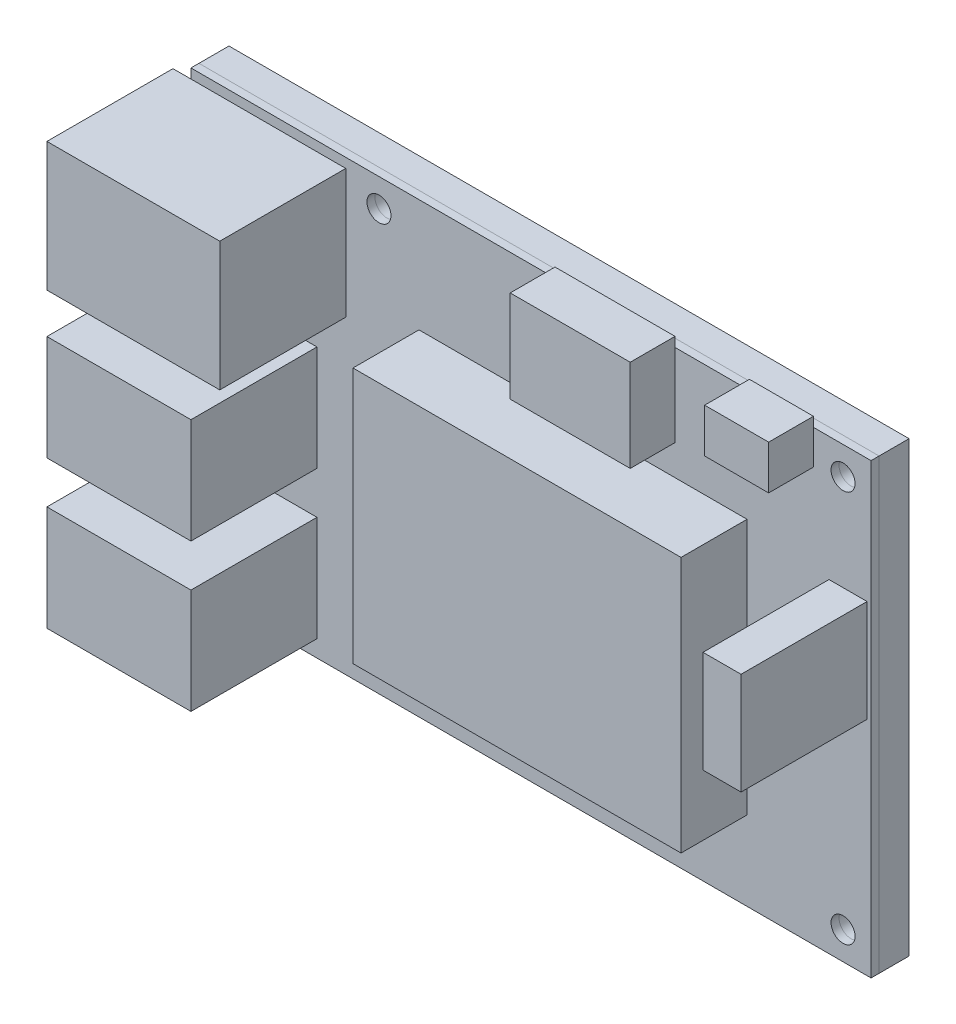
SolidWorks part; units mm, degrees
ref_plane "Front Plane" through (0, 0, 0) normal (0, 0, 1) x (1, 0, 0)
ref_plane "Top Plane" through (0, 0, 0) normal (0, 1, 0) x (1, 0, 0)
ref_plane "Right Plane" through (0, 0, 0) normal (1, 0, 0) x (0, 0, -1)
sketch "Sketch1" plane through (0, 0, 0) normal (0, 0, 1) x (1, 0, 0)
  line L0 (-19, 24.5) -> (39, 24.5) construction
  line L1 (-42.5, 28) -> (42.5, 28)
  line L2 (-42.5, 28) -> (-42.5, -28)
  line L3 (-42.5, -28) -> (42.5, -28)
  line L4 (42.5, 28) -> (42.5, -28)
  line L5 (39, 24.5) -> (39, -24.5) construction
  line L6 (39, -24.5) -> (-19, -24.5) construction
  line L7 (-19, -24.5) -> (-19, 24.5) construction
  line L8 (39, 0) -> (42.5, 0) construction
  line L9 (55, 0) -> (-55, 0) construction
  line L10 (0, -55) -> (0, 55) construction
  circle A0 centre (-19, 24.5) radius 1.5
  circle A1 centre (-19, -24.5) radius 1.5
  circle A2 centre (39, 24.5) radius 1.5
  circle A3 centre (39, -24.5) radius 1.5
  point P12 (-19, 0)
  point P17 (0, 28)
  dimension "D1" = 3
  dimension "D2" = 58
  dimension "D3" = 49
  dimension "D4" = 56
  dimension "D5" = 85
  dimension "D6" = 3.5
extrude "Boss-Extrude1" add sketch "Sketch1" along normal blind 1
extrude "Boss-Extrude2" add sketch "Sketch1<2>" against normal blind 3.75 separate body
sketch "Sketch1<2>" plane through (0, 0, 0) normal (0, 0, 1) x (1, 0, 0) same geometry as "Sketch1"
sketch "Sketch3" plane through (0, 0, 1) normal (0, 0, 1) x (1, 0, 0)
  line L0 (42.5, 28) -> (42.5, -28) construction
  line L1 (-14, 13.9) -> (27, 13.9)
  line L2 (-14, 13.9) -> (-14, -18.1)
  line L3 (-14, -18.1) -> (27, -18.1)
  line L4 (27, 13.9) -> (27, -18.1)
  line L5 (-42.5, 28) -> (42.5, 28) construction
  dimension "D1" = 41
  dimension "D2" = 32
  dimension "D3" = 15.5
  dimension "D4" = 14.1
extrude "Boss-Extrude3" add sketch "Sketch3" along normal blind 8.25
sketch "Sketch4" plane through (0, 0, 1) normal (0, 0, 1) x (1, 0, 0)
  line L0 (-44.7495, -0.89) -> (-34.7495, -0.89) construction
  line L1 (-44.7495, 5.68) -> (-26.7495, 5.68)
  line L2 (-44.7495, 5.68) -> (-44.7495, -7.46)
  line L3 (-44.7495, -7.46) -> (-26.7495, -7.46)
  line L4 (-26.7495, 5.68) -> (-26.7495, -7.46)
  line L5 (-44.7495, -12.76) -> (-26.7495, -12.76)
  line L6 (-44.7495, -12.76) -> (-44.7495, -25.9)
  line L7 (-44.7495, -25.9) -> (-26.7495, -25.9)
  line L8 (-26.7495, -12.76) -> (-26.7495, -25.9)
  line L9 (-44.7495, -19.33) -> (-34.7495, -19.33) construction
  line L10 (42.5, -28) -> (42.5, 28) construction
  line L11 (37.245, 12.5) -> (42, 12.5)
  line L12 (-44.7495, 26.8) -> (-23.1495, 26.8)
  line L13 (-44.7495, 26.8) -> (-44.7495, 10.7)
  line L14 (-44.7495, 10.7) -> (-23.1495, 10.7)
  line L15 (-23.1495, 26.8) -> (-23.1495, 10.7)
  line L16 (37.245, 12.5) -> (37.245, -0.25)
  line L17 (37.245, -0.25) -> (42, -0.25)
  line L18 (42, 12.5) -> (42, -0.25)
  line L19 (42.5, 28) -> (-42.5, 28) construction
  dimension "D1" = 18
  dimension "D2" = 13.14
  dimension "D3" = 10
  dimension "D4" = 5.3
  dimension "D5" = 2.1
  dimension "D6" = 21.6
  dimension "D7" = 1.2
  dimension "D8" = 16.1
  dimension "D9" = 4.755
  dimension "D10" = 12.75
  dimension "D11" = 0.5
  dimension "D12" = 15.5
extrude "Boss-Extrude4" add sketch "Sketch4" along normal blind 15.75
sketch "Sketch5" plane through (0, 0, 1) normal (0, 0, 1) x (1, 0, 0)
  line L1 (3, 29.2) -> (18, 29.2)
  line L2 (3, 29.2) -> (3, 17.7)
  line L3 (3, 17.7) -> (18, 17.7)
  line L4 (18, 29.2) -> (18, 17.7)
  line L5 (27.3, 29.2) -> (35.3, 29.2)
  line L6 (27.3, 29.2) -> (27.3, 23.7)
  line L7 (27.3, 23.7) -> (35.3, 23.7)
  line L8 (35.3, 29.2) -> (35.3, 23.7)
  dimension "D1" = 15
  dimension "D2" = 8
  dimension "D3" = 11.5
  dimension "D4" = 5.5
  dimension "D5" = 1.2
  dimension "D6" = 24.5
  dimension "D7" = 7.2
extrude "Boss-Extrude5" add sketch "Sketch5" along normal blind 5.6
sketch "Sketch6" plane through (0, 0, 0) normal (0, 0, 1) x (1, 0, 0)
  line L0 (-42.5, -28) -> (42.5, -28) construction
  line L1 (-0.5969, -28.5) -> (-12.2069, -28.5)
  line L2 (-0.5969, -28.5) -> (-0.5969, -12.75)
  line L3 (-0.5969, -12.75) -> (-12.2069, -12.75)
  line L4 (-12.2069, -28.5) -> (-12.2069, -12.75)
  dimension "D1" = 11.61
  dimension "D2" = 15.75
  dimension "D3" = 0.5
extrude "Boss-Extrude6" add sketch "Sketch6" against normal blind 4 separate body
